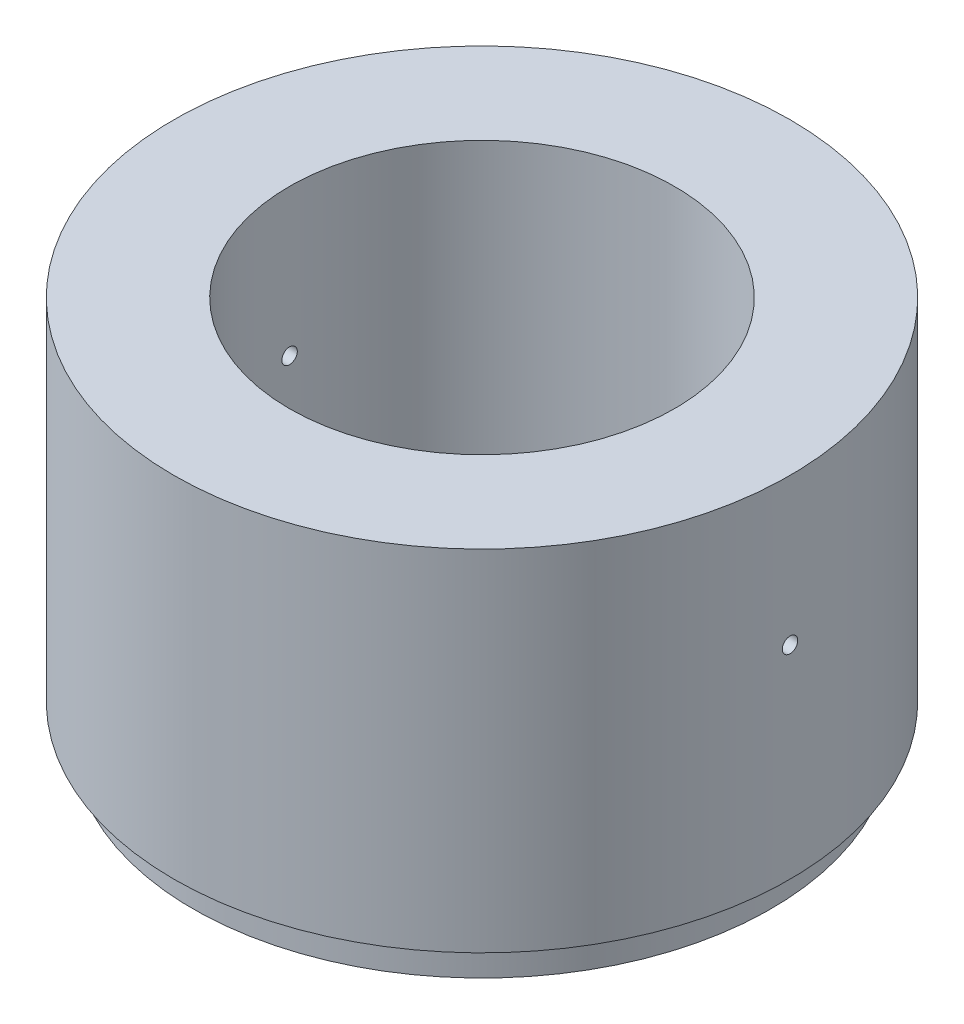
SolidWorks part; units mm, degrees
material "C (Graphite)"
ref_plane "Front Plane" through (0, 0, 0) normal (0, 0, 1) x (1, 0, 0)
ref_plane "Top Plane" through (0, 0, 0) normal (0, 1, 0) x (1, 0, 0)
ref_plane "Right Plane" through (0, 0, 0) normal (1, 0, 0) x (0, 0, -1)
sketch "Sketch1" plane through (0, 0, 0) normal (0, 1, 0) x (1, 0, 0)
  circle A0 centre (0, 0) radius 40
  circle A1 centre (0, 0) radius 25
  dimension "D1" = 80
  dimension "D2" = 50
extrude "Boss-Extrude1" add sketch "Sketch1" along normal blind 50
sketch "Sketch2" plane through (0, 0, 0) normal (0, -1, 0) x (1, 0, 0)
  circle A0 centre (0, 0) radius 37.5
  circle A1 centre (0, 0) radius 40
  dimension "D1" = 75
  dimension "D2" = 80
extrude "Cut-Extrude1" cut sketch "Sketch2" against normal blind 4.6
sketch "Sketch3" plane through (0, 0, 0) normal (1, 0, 0) x (0, 0, -1)
  line L0 (40, 50) -> (-40, 50) construction
  circle A0 centre (0, 30.95) radius 1
  dimension "D1" = 2
  dimension "D2" = 19.05
extrude "Cut-Extrude2" cut sketch "Sketch3" against normal through all both and the other way through all
